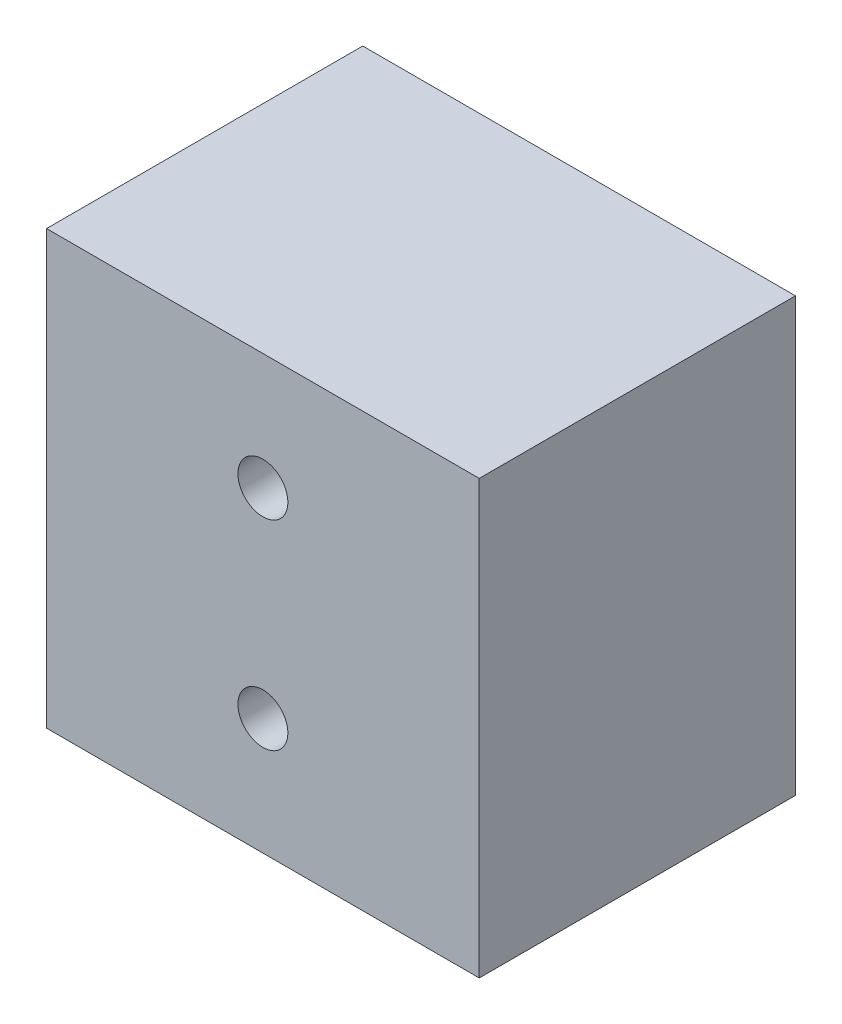
SolidWorks part; units mm, degrees
ref_plane "Front Plane" through (0, 0, 0) normal (0, 0, 1) x (1, 0, 0)
ref_plane "Top Plane" through (0, 0, 0) normal (0, 1, 0) x (1, 0, 0)
ref_plane "Right Plane" through (0, 0, 0) normal (1, 0, 0) x (0, 0, -1)
sketch "Sketch1" plane through (0, 0, 0) normal (0, 0, 1) x (1, 0, 0)
  line L1 (-10.346, 9.8512) -> (15.654, 9.8512)
  line L2 (-10.346, 9.8512) -> (-10.346, -16.1488)
  line L3 (-10.346, -16.1488) -> (15.654, -16.1488)
  line L4 (15.654, 9.8512) -> (15.654, -16.1488)
  circle A0 centre (2.654, 2.8512) radius 1.5
  circle A1 centre (2.654, -9.1488) radius 1.5
  dimension "D3" = 7
  dimension "D1" = 26
  dimension "D2" = 26
  dimension "D4" = 12
  dimension "D5" = 7
  dimension "D6" = 13
  dimension "D7" = 13
extrude "Boss-Extrude1" add sketch "Sketch1" along normal blind 20
ref_plane "Plane1" through (0, 0, 0) normal (0, 0, -1) x (-1, 0, 0)
sketch "Sketch2" plane through (0, 0, 0) normal (0, 0, -1) x (-1, 0, 0)
  circle A0 centre (-2.654, -3.1488) radius 10
  circle A1 centre (-2.654, 2.8512) radius 3
  circle A2 centre (-2.654, -9.1488) radius 3
  circle A3 centre (-2.654, 2.8512) radius 1.5
  circle A4 centre (-2.654, -9.1488) radius 1.5
  dimension "D1" = 12
extrude "Cut-Extrude1" cut sketch "Sketch2" against normal blind 15 contours A2 | A1 | A0
extrude "Cut-Extrude3" cut sketch "Sketch2<7>" against normal blind 17 contours A1 A3 | A2 A4 region at (5.5691, 2.8512, 0) region at (5.5691, -9.1488, 0)
sketch "Sketch2<7>" plane through (0, 0, 0) normal (0, 0, -1) x (-1, 0, 0) same geometry as "Sketch2"
chamfer "Chamfer1" distance 1 angle 45 4 edges at (2.654, -16.1488, 0) (-10.346, -3.1488, 0) (15.654, -3.1488, 0) (2.654, 9.8512, 0)
ref_plane "Plane2" through (0, 0, 0) normal (0, 0, -1) x (-1, 0, 0)
sketch "Sketch3" plane through (0, 0, 0) normal (0, 0, -1) x (-1, 0, 0)
  line L0 (-6.4013, 0) -> (-9.9517, 3.4666)
  line L1 (5.0437, 3.4666) -> (5.4921, 3.9149)
  line L2 (5.0437, -9.3642) -> (5.5241, -9.7752)
  line L3 (-10.1249, -9.3642) -> (-10.5084, -9.6849)
  line L4 (1.4933, -5.8976) -> (5.0437, -9.3642)
  line L5 (-5.9382, 0.535) -> (-5.938, 0.5347)
  line L6 (1.4933, 0) -> (5.0437, 3.4666)
  line L7 (-6.4013, -5.8976) -> (-10.1249, -9.3642)
  line L8 (-9.9517, 3.4666) -> (-10.4321, 3.8776)
  circle A1 centre (-2.454, -2.9488) radius 4.9271
  arc A2 (5.5241, -9.7752) -> (5.4921, 3.9149) centre (-2.454, -2.9488) ccw
  arc A3 (-9.7417, 3.8987) -> (-9.8057, -9.7276) centre (-2.454, -2.9488) ccw construction
  arc A4 (-10.4321, 3.8776) -> (-10.5084, -9.6849) centre (-2.454, -2.9488) ccw
extrude "Boss-Extrude3" add sketch "Sketch3" against normal blind 3.5 contours L2 A2 L1 L6 A1 L4 | L8 A4 L3 L7 A1 L0 region at (9.9161, -2.9147, 0) region at (-5.0031, -2.947, 0)
